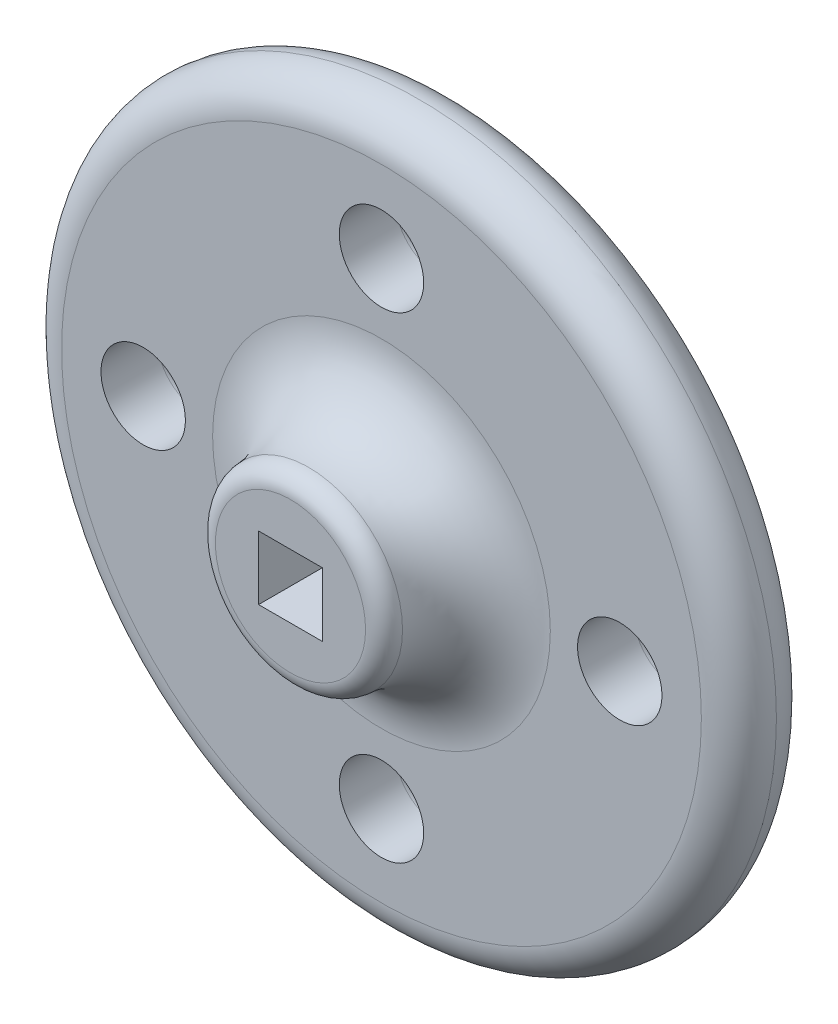
SolidWorks part; units mm, degrees
ref_plane "Front Plane" through (0, 0, 0) normal (0, 0, 1) x (1, 0, 0)
ref_plane "Top Plane" through (0, 0, 0) normal (0, 1, 0) x (1, 0, 0)
ref_plane "Right Plane" through (0, 0, 0) normal (1, 0, 0) x (0, 0, -1)
sketch "Sketch1" plane through (0, 0, 0) normal (0, 0, 1) x (1, 0, 0)
  line L1 (1.7, 1.7) -> (-1.7, 1.7)
  line L2 (1.7, 1.7) -> (1.7, -1.7)
  line L3 (1.7, -1.7) -> (-1.7, -1.7)
  line L4 (-1.7, 1.7) -> (-1.7, -1.7)
  line L5 (1.7, 1.7) -> (-1.7, -1.7) construction
  line L6 (1.7, -1.7) -> (-1.7, 1.7) construction
  circle A1 centre (12.7, 0) radius 2.25
  circle A2 centre (0, -12.7) radius 2.25
  circle A3 centre (-12.7, 0) radius 2.25
  circle A4 centre (0, 12.7) radius 2.25
  circle A5 centre (0, 0) radius 19.05
  circle A6 centre (0, 0) radius 5
  point P0 (0, 0)
  dimension "D2" = 4.5
  dimension "D5" = 38.1
  dimension "D6" = 10
  dimension "D1" = 3.4
  dimension "D3" = 12.7
  dimension "D4" = 4
extrude "Boss-Extrude1" add sketch "Sketch1" along normal blind 4 contours A5 A6 A1 A2 A3 A4 | A6 L4 L1 L2 L3 region at (-18.5112, 0, 0) region at (-4.8586, 0, 0)
extrude "Boss-Extrude2" add sketch "Sketch1<3>" along normal blind 4.85 from surface contours A6 L4 L1 L2 L3 region at (-4.8586, 0, 0) starting at face at (14.95, 0, 4)
sketch "Sketch1<3>" plane through (0, 0, 0) normal (0, 0, 1) x (1, 0, 0) same geometry as "Sketch1"
fillet "Fillet1" radius 4 1 edges at (5, 0, 4)
fillet "Fillet2" radius 1 1 edges at (5, 0, 8.85)
fillet "Fillet3" radius 2 2 edges at (19.05, 0, 0) (19.05, 0, 4)
fillet "Fillet4" radius 1 8 edges at (2.25, -12.7, 0) (-10.45, 0, 0) (1.7, 0, 0) (0, 1.7, 0) (-1.7, 0, 0) (0, -1.7, 0) (14.95, 0, 0) (2.25, 12.7, 0)
